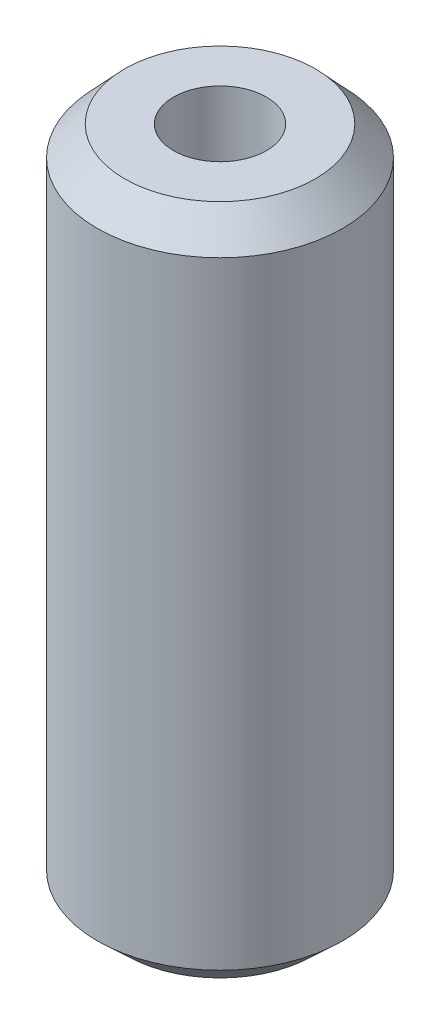
SolidWorks part; units mm, degrees
ref_plane "Front Plane" through (0, 0, 0) normal (0, 0, 1) x (1, 0, 0)
ref_plane "Top Plane" through (0, 0, 0) normal (0, 1, 0) x (1, 0, 0)
ref_plane "Right Plane" through (0, 0, 0) normal (1, 0, 0) x (0, 0, -1)
sketch "Sketch1" plane through (0, 0, 0) normal (0, 1, 0) x (1, 0, 0)
  circle A0 centre (0, 0) radius 5
  dimension "SHAFT_OD" = 10
extrude "Boss-Extrude1" add sketch "Sketch1" along normal blind 27.4567
sketch "Sketch2" plane through (0, 0, 0) normal (0, 1, 0) x (1, 0, 0)
  circle A0 centre (0, 0) radius 1.8941
  dimension "BORE_D" = 3.7881
extrude "Cut-Extrude1" cut sketch "Sketch2" along normal through all
chamfer "Chamfer1" distance 1.1923 angle 43.072 2 edges at (0, 27.4567, 5) (0, 0, 5) first distance on face at (0, 27.4567, 5) first distance on face at (0, 0, 1.8941)
